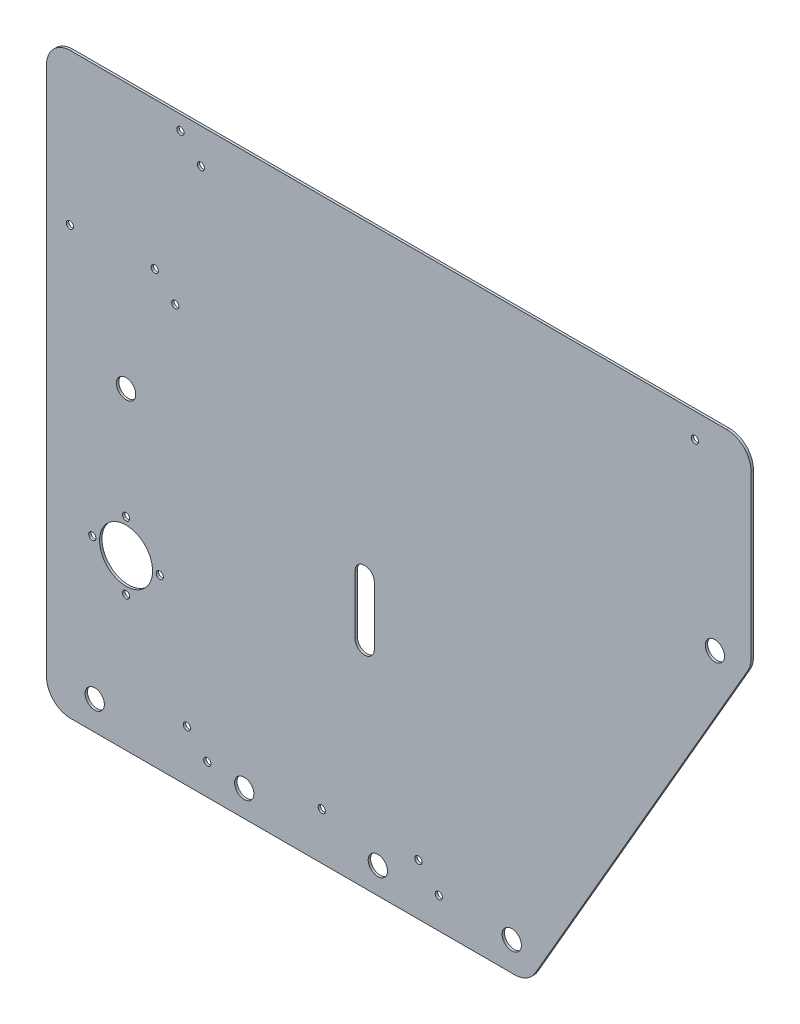
SolidWorks part; units mm, degrees
ref_plane "Front Plane" through (0, 0, 0) normal (0, 0, 1) x (1, 0, 0)
ref_plane "Top Plane" through (0, 0, 0) normal (0, 1, 0) x (1, 0, 0)
ref_plane "Right Plane" through (0, 0, 0) normal (1, 0, 0) x (0, 0, -1)
sketch "Sketch1" plane through (0, 0, 0) normal (0, 0, 1) x (1, 0, 0)
  line L0 (100, 80) -> (192.376, 80)
  line L1 (-100, -80) -> (100, -80)
  line L2 (-100, -80) -> (-100, 80)
  line L3 (-100, 80) -> (100, 80)
  line L4 (100, -80) -> (100, 80)
  line L5 (-100, -80) -> (100, 80) construction
  line L6 (-100, 80) -> (100, -80) construction
  line L7 (192.376, 80) -> (100, -80)
  line L8 (100, 80) -> (100, -80)
  line L10 (-100, 80) -> (192.376, 80)
  line L11 (-100, 80) -> (-100, 110)
  line L12 (-100, 110) -> (192.376, 110)
  line L13 (192.376, 80) -> (192.376, 110)
  point P0 (0, 0)
  dimension "D1" = 160
  dimension "D2" = 200
  dimension "D3" = 30
  dimension "D4" = 30
extrude "Boss-Extrude1" add sketch "Sketch1" along normal blind 1 contours L1 L4 L3 L2 | L7 L0 L4 | L11 L10 L13 L12 region at (0, 0, 0) region at (130.792, 26.6667, 0)
sketch "Sketch2" plane through (0, 0, 1) normal (0, 0, 1) x (1, 0, 0)
  line L0 (-100, -80) -> (100, -80) construction
  line L1 (192.376, 80) -> (100, -80) construction
  line L2 (-100, -80) -> (-100, 110) construction
  line L3 (-100, 110) -> (192.376, 110) construction
  line L4 (-67, -10) -> (-67, 70) construction
  line L7 (-100, -80) -> (-100, 110) construction
  line L15 (-100, -80) -> (-100, 110) construction
  line L18 (32.0262, 32) -> (32.0262, 7.7776) construction
  line L19 (36.0262, 32) -> (36.0262, 7.7776)
  line L20 (28.0262, 32) -> (28.0262, 7.7776)
  circle A0 centre (93.0718, -68) radius 4
  circle A1 centre (177.3649, 78) radius 4
  circle A2 centre (-67, -10) radius 11
  circle A3 centre (-80, -68) radius 4
  circle A4 centre (-53, -10) radius 1.5
  circle A5 centre (-67, 4) radius 1.5
  circle A6 centre (-81, -10) radius 1.5
  circle A7 centre (-67, -24) radius 1.5
  circle A10 centre (32.0262, 20) radius 4 construction
  circle A32 centre (62.7961, -67.2426) radius 1.5
  circle A33 centre (54.3108, -58.7574) radius 1.5
  circle A34 centre (-33.2742, -67.2426) radius 1.5
  circle A35 centre (-41.7595, -58.7574) radius 1.5
  circle A36 centre (14.2259, -60.5) radius 1.5
  circle A37 centre (-46.589, 90.4743) radius 1.5
  circle A38 centre (-55.0743, 98.9596) radius 1.5
  circle A39 centre (-90.2956, 97.2169) radius 1.5
  circle A40 centre (169.0558, 149.7306) radius 1.5
  arc A41 (36.0262, 32) -> (28.0262, 32) centre (32.0262, 32) ccw
  arc A42 (28.0262, 7.7776) -> (36.0262, 7.7776) centre (32.0262, 7.7776) ccw
  circle A43 centre (-17.9479, -69.1174) radius 4
  circle A44 centre (37.4944, -69.1174) radius 4
  circle A45 centre (-67, -10) radius 40 construction
  circle A46 centre (-67, 50) radius 20 construction
  circle A47 centre (-67, 50) radius 4
  point P65 (32.0262, 19.8888)
  dimension "D3" = 8
  dimension "D4" = 8
  dimension "D9" = 22
  dimension "D10" = 8
  dimension "D12" = 3
  dimension "D13" = 3
  dimension "D14" = 3
  dimension "D15" = 3
  dimension "D16" = 14
  dimension "D20" = 60
  dimension "D22" = 8
  dimension "D23" = 3
  dimension "D24" = 20
  dimension "D25" = 3
  dimension "D26" = 40
  dimension "D27" = 8
  dimension "D1" = 12
  dimension "D2" = 12
  dimension "D5" = 32
  dimension "D6" = 12
  dimension "D7" = 33
  dimension "D8" = 70
  dimension "D11" = 12
  dimension "D17" = 14
  dimension "D18" = 14
  dimension "D19" = 14
  dimension "D21" = 90
  dimension "D28" = 4
  dimension "D29" = 24.2224
  dimension "D30" = 12
  dimension "D31" = 132.0262
extrude "Cut-Extrude1" cut sketch "Sketch2" against normal blind 3
sketch "Sketch3" plane through (0, 0, 1) normal (0, 0, 1) x (1, 0, 0)
  line L0 (192.376, 80) -> (192.376, 110) construction
  line L1 (-100, 110) -> (192.376, 110)
  line L2 (-100, 110) -> (-100, 160)
  line L3 (-100, 160) -> (192.376, 160)
  line L4 (192.376, 110) -> (192.376, 160)
  dimension "D1" = 50
extrude "Boss-Extrude2" add sketch "Sketch3" against normal blind 1
fillet "Fillet1" radius 10 5 edges at (100, -80, 0.5) (-100, -80, 0.5) (-100, 160, 0.5) (192.376, 160, 0.5) (192.376, 80, 0.5)
sketch "Sketch4" plane through (0, 0, 1) normal (0, 0, 1) x (1, 0, 0)
  circle A2 centre (-44.4423, 153.9596) radius 1.5
  circle A3 centre (-35.957, 145.4743) radius 1.5
  circle A4 centre (169.0558, 149.7306) radius 1.5
  dimension "D1" = 3
extrude "Cut-Extrude2" cut sketch "Sketch4" against normal blind 11
